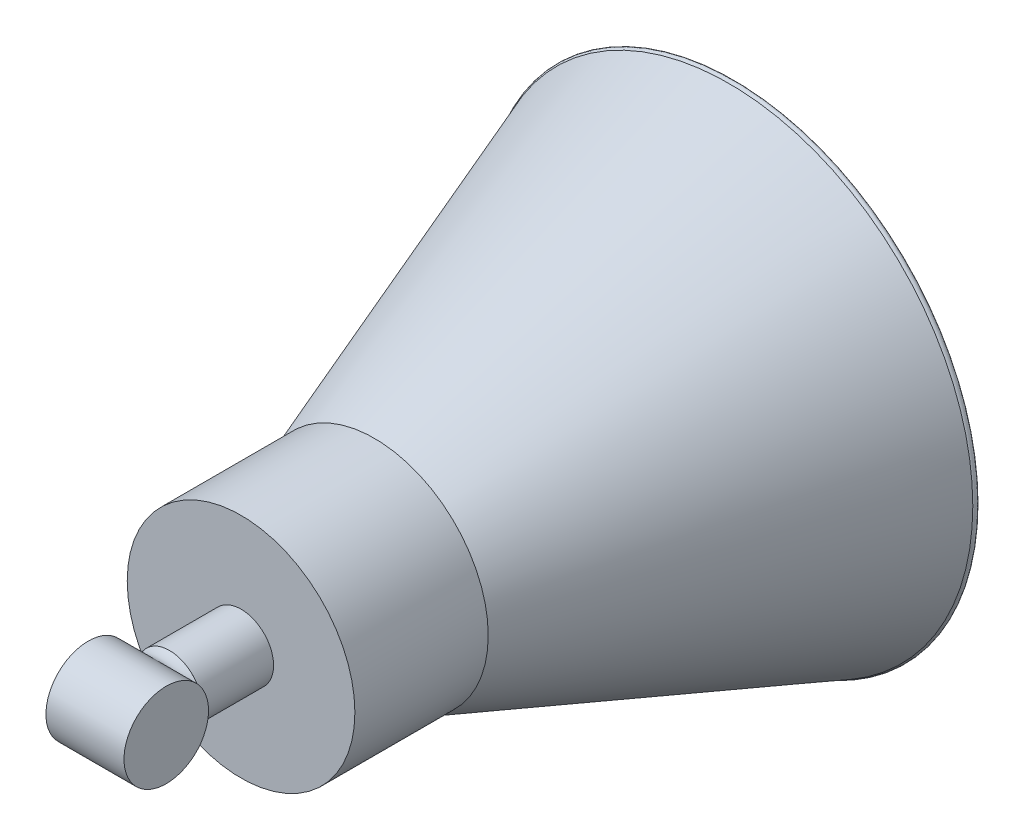
SolidWorks part; units mm, degrees
ref_plane "Front Plane" through (0, 0, 0) normal (0, 0, 1) x (1, 0, 0)
ref_plane "Top Plane" through (0, 0, 0) normal (0, 1, 0) x (1, 0, 0)
ref_plane "Right Plane" through (0, 0, 0) normal (1, 0, 0) x (0, 0, -1)
sketch "Sketch1" plane through (0, 0, 0) normal (0, 0, 1) x (1, 0, 0)
  circle A0 centre (0, 0) radius 20
extrude "Boss-Extrude1" add sketch "Sketch1" along normal blind 20
sketch "Sketch2" plane through (0, 0, 0) normal (0, 0, 1) x (1, 0, 0)
  circle A0 centre (0, 0) radius 19
extrude "Cut-Extrude1" cut sketch "Sketch2" along normal blind 19
sketch "Sketch4" plane through (0, 0, 0) normal (0, 1, 0) x (1, 0, 0)
  line L0 (20, 0) -> (20, 70)
  line L1 (-20, 0) -> (-20, 20)
  line L2 (-20, 20) -> (-30, 20)
  line L3 (-20, 20) -> (-20, 30)
  line L4 (-31.7492, 30) -> (-31.355, 30.3075)
  line L5 (0, 0) -> (0, 33.0419) construction
  line L6 (-20, 0) -> (-19, 0)
  arc A0 (-20, 0) -> (-31.7492, 30) centre (-62.7551, 0.5561) ccw
  arc A1 (-31.355, 30.3075) -> (-19, 0) centre (-60.9017, 0.5906) cw
revolve "Revolve1" add sketch "Sketch4" angle 360 about L5
sketch "Sketch5" plane through (0, 0, 0) normal (0, 1, 0) x (1, 0, 0)
  line L0 (31.355, 30.3075) -> (-31.355, 30.3075) construction
  line L1 (0, 85.0016) -> (0, 84.0563)
  line L2 (-31.7492, 30) -> (-31.2756, 29.9836)
  line L3 (0, 85.0016) -> (0, 30.3075) construction
  arc A0 (-31.7492, 30) -> (0, 85.0016) centre (-0.2865, 48.5027) cw
  arc A1 (0, 84.0563) -> (-31.2756, 29.9836) centre (1.6032, 47.0477) ccw
revolve "Revolve2" add sketch "Sketch5" angle 360 about L3
sketch "Sketch7" plane through (0, 0, 20) normal (0, 0, 1) x (1, 0, 0)
  circle A0 centre (0, 0) radius 35
  circle A1 centre (0, 0) radius 34
extrude "Boss-Extrude4" add sketch "Sketch7" against normal blind 40 separate body
sketch "Sketch8" plane through (0, 0, 20) normal (0, 0, 1) x (1, 0, 0)
  circle A0 centre (0, 0) radius 35
extrude "Boss-Extrude5" add sketch "Sketch8" along normal blind 1 contours A0
sketch "Sketch10" plane through (0, 0, 0) normal (1, 0, 0) x (0, 0, -1)
  line L2 (-21, 35) -> (-21, -35) construction
  line L3 (-21, 0) -> (129, 0) construction
  line L4 (20, 35) -> (129, 75)
  line L5 (20, 34) -> (129, 74)
  line L6 (20, 35) -> (20, 34)
  arc A1 (129, 74) -> (129, 75) centre (129.7817, 74.5) ccw
revolve "Revolve3" add sketch "Sketch10" angle 360 about L3
sketch "Sketch11" plane through (0, 0, 21) normal (0, 0, 1) x (1, 0, 0)
  circle A0 centre (0, 0) radius 10
extrude "Boss-Extrude6" add sketch "Sketch11" along normal blind 22
sketch "Sketch13" plane through (0, 0, 0) normal (1, 0, 0) x (0, 0, -1)
  line L0 (-43, 0) -> (-56, 0)
  line L1 (-43, 10) -> (-43, -10) construction
  circle A0 centre (-56, 0) radius 13
extrude "Boss-Extrude8" add sketch "Sketch13" along normal blind 12 and the other way blind 12 separate body contours A0 region at (0, 0, 68.6323)
sketch "Sketch14" plane through (0, 0, 0) normal (1, 0, 0) x (0, 0, -1)
  line L0 (0, 0) -> (-74.4098, 0) construction
  arc A0 (-48.596, 10.6856) -> (-43, 10) centre (-45.4552, 13.1408) ccw
  circle A1 centre (-56, 0) radius 13 construction
  arc A2 (-48.596, 10.6856) -> (-43, 10) centre (-45.4117, 13.496) ccw
revolve "Revolve4" add sketch "Sketch14" angle 360 about L0
